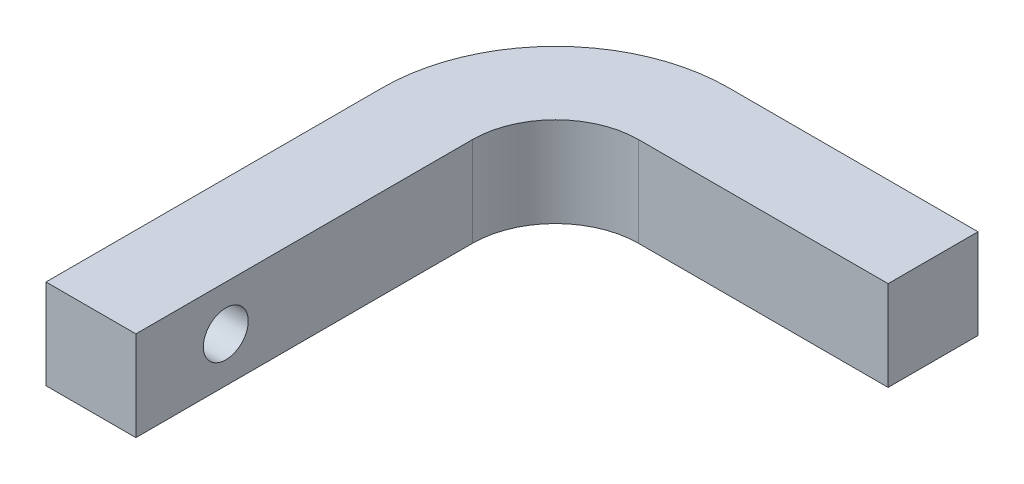
SolidWorks part; units mm, degrees
ref_plane "Front Plane" through (0, 0, 0) normal (0, 0, 1) x (1, 0, 0)
ref_plane "Top Plane" through (0, 0, 0) normal (0, 1, 0) x (1, 0, 0)
ref_plane "Right Plane" through (0, 0, 0) normal (1, 0, 0) x (0, 0, -1)
ref_axis "Z" through (0, 0, -2.225) along (0, 0, 1)
sketch "Sketch1" plane through (0, 0, 0) normal (0, 1, 0) x (1, 0, 0)
  line L0 (-11.1, 0) -> (11.1, 0)
  line L1 (-26.5, -15.4) -> (-26.5, -45.34)
  line L2 (-26.5, -45.34) -> (-18.5, -45.34)
  line L3 (-18.5, -45.34) -> (-18.5, -15.4)
  line L4 (-11.1, -8) -> (11.1, -8)
  line L5 (0, -8) -> (0, 0) construction
  line L6 (18.5, -45.34) -> (18.5, -15.4) construction
  line L7 (26.5, -45.34) -> (18.5, -45.34) construction
  line L8 (26.5, -15.4) -> (26.5, -45.34) construction
  line L9 (11.1, 0) -> (11.1, -8)
  arc A0 (-11.1, 0) -> (-26.5, -15.4) centre (-11.1, -15.4) ccw
  arc A1 (-18.5, -15.4) -> (-11.1, -8) centre (-11.1, -15.4) cw
  arc A2 (18.5, -15.4) -> (11.1, -8) centre (11.1, -15.4) ccw construction
  arc A3 (11.1, 0) -> (26.5, -15.4) centre (11.1, -15.4) cw construction
  dimension "D3" = 7.4
  dimension "D1" = 37
  dimension "D2" = 8
  dimension "D4" = 37.34
extrude "Boss-Extrude1" add sketch "Sketch1" along normal blind 4 and the other way blind 4
sketch "Sketch2" plane through (-18.5, 0, 0) normal (-1, 0, 0) x (0, 0, 1)
  line L1 (20.68, 0) -> (-20.68, 0) construction
  line L2 (0, -4.4) -> (0, 4.4) construction
  circle A0 centre (37.34, 0) radius 2
  dimension "D1" = 4
  dimension "D2" = 37.34
extrude "Cut-Extrude1" cut sketch "Sketch2" against normal through all both and the other way through all
ref_axis "Axis2" through (-60.1767, 0, 37.34) along (1, 0, 0)
equation "\"width\"= \"EyeDiameter\" + \"EyeClearance\""
equation "\"prongwidth\"= 8"
equation "\"D2@Sketch1\"=\"prongwidth\""
equation "\"D3@Sketch1\"=\"width\"/5"
equation "\"pronglength\"= \"BasePlaneDistance\"'model implicitly adds clearance (of prongwidth) to the hole drilled at the baseplanedistance"
equation "\"D4@Sketch1\"=\"pronglength\""
equation "\"D1@Boss-Extrude1\"=\"prongwidth\"/2"
equation "\"D2@Boss-Extrude1\"=\"prongwidth\"/2"
equation "\"lbracket-plane-to-axis\"= \"BasePlaneDistance\""
equation "\"D2@Sketch2\"=\"lbracket-plane-to-axis\""
equation "\"EyeDiameter\" = 35"
equation "\"BasePlaneDistance\" = \"EyeDiameter\"/2+19.84"
equation "\"EyeClearance\" = 2"
equation "\"D1@Sketch1\"=\"EyeDiameter\"+\"EyeClearance\""
